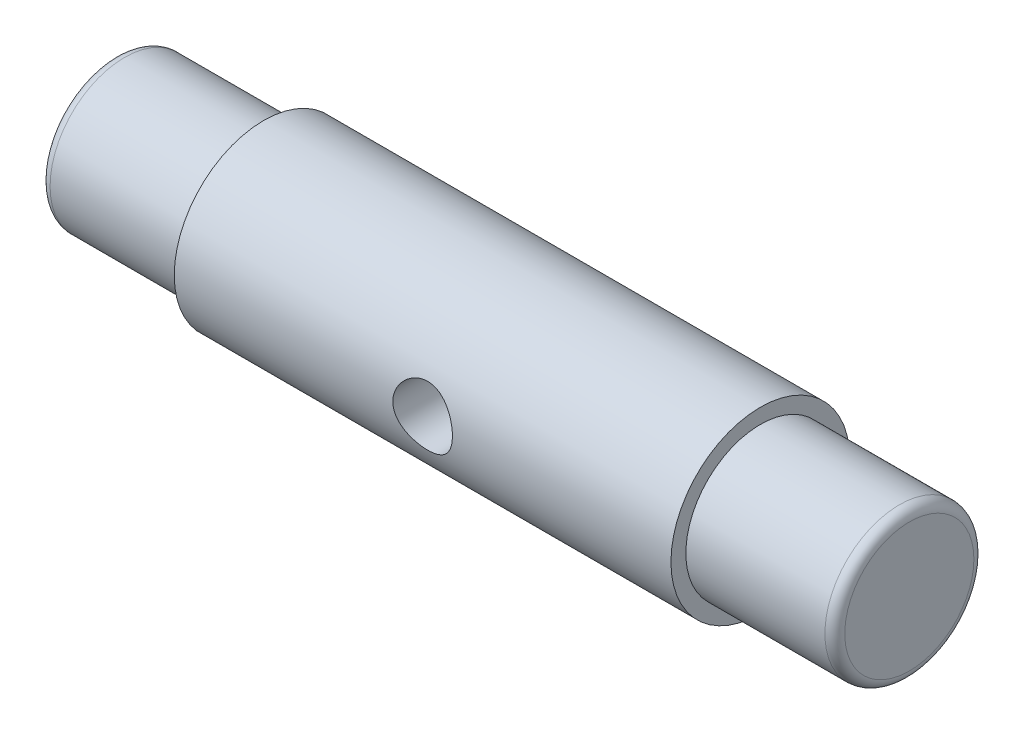
SolidWorks part; units mm, degrees
material "Ductile Iron"
ref_plane "Front Plane" through (0, 0, 0) normal (0, 0, 1) x (1, 0, 0)
ref_plane "Top Plane" through (0, 0, 0) normal (0, 1, 0) x (1, 0, 0)
ref_plane "Right Plane" through (0, 0, 0) normal (1, 0, 0) x (0, 0, -1)
sketch "Sketch1" plane through (0, 0, 0) normal (1, 0, 0) x (0, 0, -1)
  circle A0 centre (0, 0) radius 9
  dimension "D1" = 18
extrude "Boss-Extrude2" add sketch "Sketch1" along normal blind 25 and the other way blind 25
sketch "Sketch2" plane through (25, 0, 0) normal (1, 0, 0) x (0, 0, -1)
  circle A0 centre (0, 0) radius 7.5
  dimension "D1" = 15
extrude "Boss-Extrude3" add sketch "Sketch2" along normal blind 15
mirror "Mirror1" about plane through (0, 0, 0) normal (1, 0, 0) of "Boss-Extrude3"
fillet "Fillet2" radius 1 2 edges at (40, 0, -7.5) (-40, 0, -7.5)
sketch "Sketch3" plane through (0, 0, 0) normal (0, 0, 1) x (1, 0, 0)
  circle A0 centre (0, 0) radius 3
  dimension "D1" = 6
extrude "Cut-Extrude1" cut sketch "Sketch3" against normal through all and the other way through all
